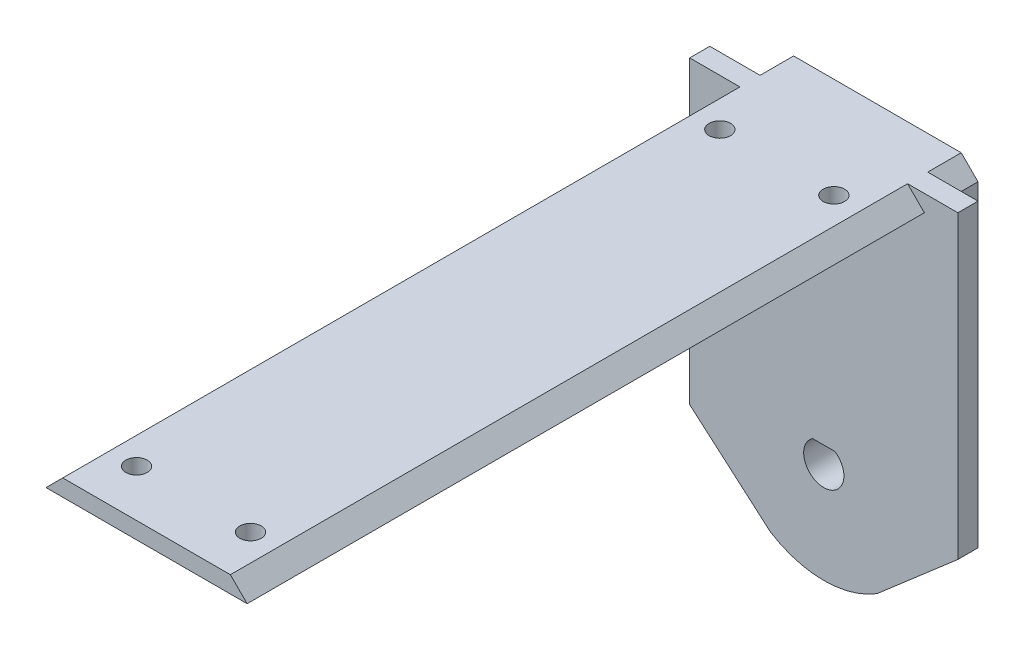
SolidWorks part; units mm, degrees
note: The reader was unsure of these and kept them because the rebuilt part matched: shared geometry of "Sketch1<5>".
material "ABS"
ref_plane "Front Plane" through (0, 0, 0) normal (0, 0, 1) x (1, 0, 0)
ref_plane "Top Plane" through (0, 0, 0) normal (0, 1, 0) x (1, 0, 0)
ref_plane "Right Plane" through (0, 0, 0) normal (1, 0, 0) x (0, 0, -1)
sketch "Sketch1" plane through (0, 0, 0) normal (0, 0, 1) x (1, 0, 0)
  line L0 (0, 0) -> (0, -7) construction
  line L1 (5, -15.6603) -> (-5, -15.6603) construction
  line L2 (15, 33) -> (-15, 33)
  line L3 (15, -7) -> (-15, -7) construction
  line L4 (15, -7) -> (15, 33)
  line L5 (-15, -7) -> (-15, 33)
  line L6 (15, -7) -> (5, -15.6603)
  line L7 (-5, -15.6603) -> (-15, -7)
  line L8 (15, 33) -> (15, 35.5) construction
  line L9 (15, 35.5) -> (-15, 35.5) construction
  line L10 (-15, 35.5) -> (-15, 33) construction
  line L11 (-15, 33) -> (-12.5, 35.5)
  line L12 (15, 33) -> (12.5, 35.5)
  line L13 (-12.5, 35.5) -> (12.5, 35.5)
  line L14 (1.6583, -4.5) -> (-1.6583, -4.5)
  circle A1 centre (0, -7) radius 10 construction
  arc A2 (-1.6583, -4.5) -> (1.6583, -4.5) centre (0, -7) ccw
  arc A3 (5, -15.6603) -> (-5, -15.6603) centre (0, -7) cw
  point P1 (0, -7)
  point P6 (0, -15.6603)
  dimension "D1" = 30
  dimension "D3" = 20
  dimension "D4" = 6
  dimension "D5" = 10
  dimension "D2" = 7
  dimension "D6" = 40
  dimension "D7" = 2.5
  dimension "D8" = 45
  dimension "D9" = 45
  dimension "D10" = 2.5
extrude "Boss-Extrude1" add sketch "Sketch1" along normal blind 8
extrude "Boss-Extrude3" add sketch "Sketch1<5>" along normal blind 109 contours L13 L11 L2 L12
sketch "Sketch1<5>" plane through (0, 0, 0) normal (0, 0, 1) x (1, 0, 0) same geometry as "Sketch1"
hole_wizard "M3 Clearance Slot1" positions "Sketch5" profile "Sketch4" size "M3" standard "ANSI Metric" slot yes end condition through all
sketch "Sketch5" plane through (0, 35.5, 0) normal (0, 1, 0) x (1, 0, 0)
  line L4 (-8.5, 0) -> (-8.5, -109) construction
  line L5 (-12.5, 0) -> (12.5, 0) construction
  line L6 (-12.5, -109) -> (12.5, -109) construction
  line L8 (-12.5, -109) -> (-12.5, 0) construction
  line L9 (8.5, 0) -> (8.5, -109) construction
  line L11 (12.5, -109) -> (12.5, 0) construction
  line L12 (-12.5, -102) -> (12.5, -102) construction
  line L14 (-12.5, -15) -> (12.5, -15) construction
  point P0 (-8.5, -15)
  point P4 (8.5, -15)
  point P6 (-8.5, -102)
  point P8 (8.5, -102)
  dimension "D1" = 4
  dimension "D2" = 4
  dimension "D3" = 7
  dimension "D4" = 15
sketch "Sketch4" plane through (-8.5, 35.5, 15) normal (1, 0, 0) x (0, 0, 1)
  line L0 (0, 0) -> (0, 52.5)
  line L1 (0, 52.5) -> (1.6, 52.5)
  line L2 (1.6, 52.5) -> (1.6, 0)
  line L5 (1.6, 0) -> (0, 0)
  line L11 (0, -6.35) -> (0, 107.95) construction
  dimension "Thru Hole Dia." = 3.2
  dimension "Thru Hole Depth" = 52.5
sketch "Sketch6" plane through (0, 0, 8) normal (0, 0, 1) x (1, 0, 0)
  line L0 (-20, 35.5) -> (20, 35.5)
  line L1 (-12.5, 35.5) -> (12.5, 35.5) construction
  line L2 (1.6583, -4.5) -> (-1.6583, -4.5) construction
  line L3 (1.6583, -4.5) -> (-1.6583, -4.5)
  line L8 (-20, 33) -> (-20, 35.5)
  line L11 (20, 35.5) -> (20, 33)
  line L12 (20, -9.2843) -> (20, 33)
  line L13 (7.9496, -19.7202) -> (20, -9.2843)
  line L14 (-20, -9.2843) -> (-7.9496, -19.7202)
  line L15 (-20, 33) -> (-20, -9.2843)
  line L16 (20, -9.2843) -> (20, 33)
  line L17 (7.9496, -19.7202) -> (20, -9.2843)
  line L18 (-20, -9.2843) -> (-7.9496, -19.7202)
  line L19 (-20, 33) -> (-20, -9.2843)
  arc A0 (-1.6583, -4.5) -> (1.6583, -4.5) centre (0, -7) ccw construction
  arc A1 (-1.6583, -4.5) -> (1.6583, -4.5) centre (0, -7) ccw
  arc A2 (-7.9496, -19.7202) -> (7.9496, -19.7202) centre (0, -7) ccw
  arc A3 (-7.9496, -19.7202) -> (7.9496, -19.7202) centre (0, -7) ccw
  dimension "D1" = 5
extrude "Boss-Extrude4" add sketch "Sketch6" against normal blind 3
